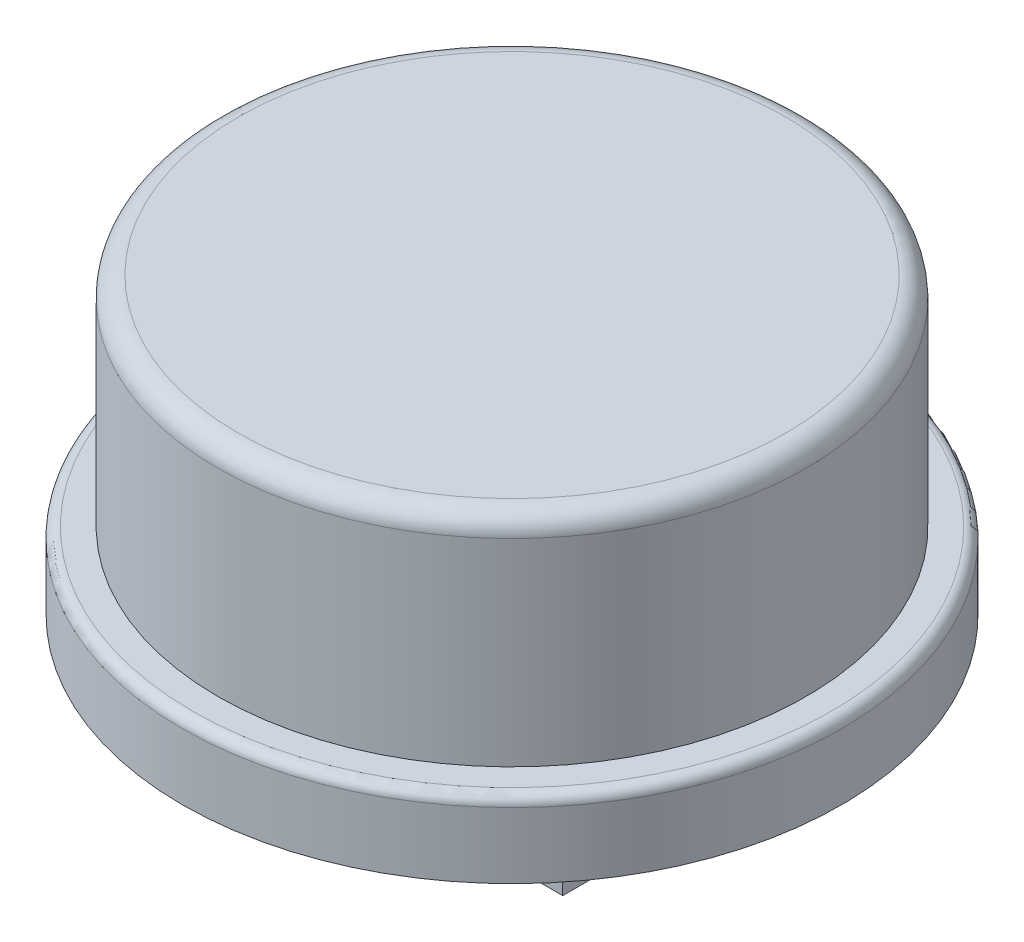
SolidWorks part; units mm, degrees
ref_plane "Front Plane" through (0, 0, 0) normal (0, 0, 1) x (1, 0, 0)
ref_plane "Top Plane" through (0, 0, 0) normal (0, 1, 0) x (1, 0, 0)
ref_plane "Right Plane" through (0, 0, 0) normal (1, 0, 0) x (0, 0, -1)
sketch "Sketch1" plane through (0, 0, 0) normal (0, 1, 0) x (1, 0, 0)
  circle A0 centre (0, 0) radius 6.5
  dimension "D1" = 13
extrude "Boss-Extrude1" add sketch "Sketch1" along normal blind 1.5
sketch "Sketch2" plane through (0, 1.5, 0) normal (0, 1, 0) x (1, 0, 0)
  circle A0 centre (0, 0) radius 5.8
  dimension "D1" = 11.6
extrude "Boss-Extrude2" add sketch "Sketch2" along normal blind 4.3
fillet "Fillet1" radius 0.4 1 edges at (0, 5.8, 5.8)
sketch "Sketch3" plane through (0, 0, 0) normal (0, -1, 0) x (1, 0, 0)
  circle A0 centre (0, 0) radius 5
  dimension "D1" = 10
extrude "Cut-Extrude1" cut sketch "Sketch3" against normal blind 4.8
sketch "Sketch4" plane through (0, 4.8, 0) normal (0, -1, 0) x (1, 0, 0)
  line L0 (-4.991, 0.3) -> (-2.9, 0.3)
  line L1 (-4.991, -0.3) -> (-2.9, -0.3)
  line L2 (-5, 0) -> (5, 0) construction
  line L3 (-2.9, 0.3) -> (-2.9, -0.3)
  line L4 (0, -3.19) -> (0, 3.19) construction
  line L5 (2.9, 0.3) -> (2.9, -0.3)
  line L6 (4.991, -0.3) -> (2.9, -0.3)
  line L7 (4.991, 0.3) -> (2.9, 0.3)
  line L8 (0, 5) -> (0, -5) construction
  line L9 (-0.3, 4.991) -> (-0.3, 2.7)
  line L10 (0.3, 4.991) -> (0.3, 2.7)
  line L11 (0.3, 2.7) -> (-0.3, 2.7)
  line L12 (0.3, -2.7) -> (-0.3, -2.7)
  line L13 (0.3, -4.991) -> (0.3, -2.7)
  line L14 (-0.3, -4.991) -> (-0.3, -2.7)
  circle A0 centre (0, 0) radius 5 construction
  circle A1 centre (0, 0) radius 5 construction
  arc A2 (-0.3, -4.991) -> (0.3, -4.991) centre (0, 0) ccw
  circle A3 centre (0, 0) radius 5
  arc A4 (-4.991, 0.3) -> (-4.991, -0.3) centre (0, 0) ccw
  arc A5 (4.991, -0.3) -> (4.991, 0.3) centre (0, 0) ccw
  arc A6 (0.3, 4.991) -> (-0.3, 4.991) centre (0, 0) ccw
  point P11 (-2.9, 0)
  point P25 (0, 2.7)
  dimension "D1" = 5.8
  dimension "D2" = 0.6
  dimension "D3" = 5.4
  dimension "D4" = 0
extrude "Boss-Extrude3" add sketch "Sketch4" along normal up to surface (4.8 mm away) up to face at (0, 0, -5)
sketch "Sketch5" plane through (0, 4.8, 0) normal (0, -1, 0) x (1, 0, 0)
  line L0 (-2.9, 0.3) -> (-2.9, -0.3) construction
  line L1 (-1, 2.7) -> (1, 2.7)
  line L2 (-1, 2.7) -> (-1, 1.9)
  line L3 (-1, 1.9) -> (1, 1.9)
  line L4 (1, 2.7) -> (1, 1.9)
  line L5 (-2.9, 1.9) -> (-1.9, 1.9)
  line L6 (-2.9, 1.9) -> (-2.9, -1.9)
  line L7 (-2.9, -1.9) -> (-1.9, -1.9)
  line L8 (-1.9, 1.9) -> (-1.9, -1.9)
  line L9 (0.3, 2.7) -> (-0.3, 2.7) construction
  line L10 (0, -3.19) -> (0, 3.19) construction
  line L11 (1.9, 1.9) -> (1.9, -1.9)
  line L12 (2.9, -1.9) -> (1.9, -1.9)
  line L13 (2.9, 1.9) -> (2.9, -1.9)
  line L14 (2.9, 1.9) -> (1.9, 1.9)
  line L15 (3.19, 0) -> (-3.19, 0) construction
  line L16 (1, -2.7) -> (1, -1.9)
  line L17 (-1, -1.9) -> (1, -1.9)
  line L18 (-1, -2.7) -> (-1, -1.9)
  line L19 (-1, -2.7) -> (1, -2.7)
  point P4 (0, 2.7)
  point P10 (-1.9, 0)
  dimension "D1" = 3.8
  dimension "D2" = 2
  dimension "D3" = 1
extrude "Boss-Extrude4" add sketch "Sketch5" along normal blind 7.2
sketch "Sketch6" plane through (0, 0, 1.9) normal (0, 0, 1) x (1, 0, 0)
  line L0 (-1.9, -1.4) -> (-1.6, -1.7)
  line L1 (-1.9, -2.4) -> (-1.9, 4.8) construction
  line L2 (-1.6, -1.7) -> (-2.4, -2.4)
  line L3 (-1.9, -2.4) -> (-2.9, -2.4) construction
  line L4 (-2.9, -2.4) -> (-2.9, 4.8) construction
  line L5 (-1.9, -1.4) -> (-1.9, -2.4)
  line L6 (-1.9, -2.4) -> (-2.4, -2.4)
  line L7 (0, -4.51) -> (0, 4.51) construction
  line L8 (1.9, -2.4) -> (2.4, -2.4)
  line L9 (1.9, -1.4) -> (1.9, -2.4)
  line L10 (1.6, -1.7) -> (2.4, -2.4)
  line L11 (1.9, -1.4) -> (1.6, -1.7)
  line M2 (1.9, 4.8) -> (1.9, -2.4)
  line M3 (1.9, -2.4) -> (2.9, -2.4)
  dimension "D1" = 1.3
  dimension "D2" = 1
  dimension "D3" = 0.7
extrude "Cut-Extrude2" cut sketch "Sketch6" against normal up to next contours L6 L5 L2 | L10 L9 M3 region at (-2.0667, -2.2542, 1.9) region at (2.0667, -2.2542, 1.9)
extrude "Boss-Extrude5" add sketch "Sketch6<3>" against normal up to surface (3.8 mm away) contours L0 L5 L2 | L11 L10 M2 region at (-1.8, -1.6875, 1.9) region at (1.8, -1.6875, 1.9) up to face at (2.4, 0.5675, -1.9)
sketch "Sketch6<3>" plane through (0, 0, 1.9) normal (0, 0, 1) x (1, 0, 0) same geometry as "Sketch6"
fillet "Fillet2" radius 0.1 2 edges at (1.6, -1.7, 0) (-1.6, -1.7, 0)
fillet "Fillet3" radius 0.2 1 edges at (0, 1.5, 6.5)
